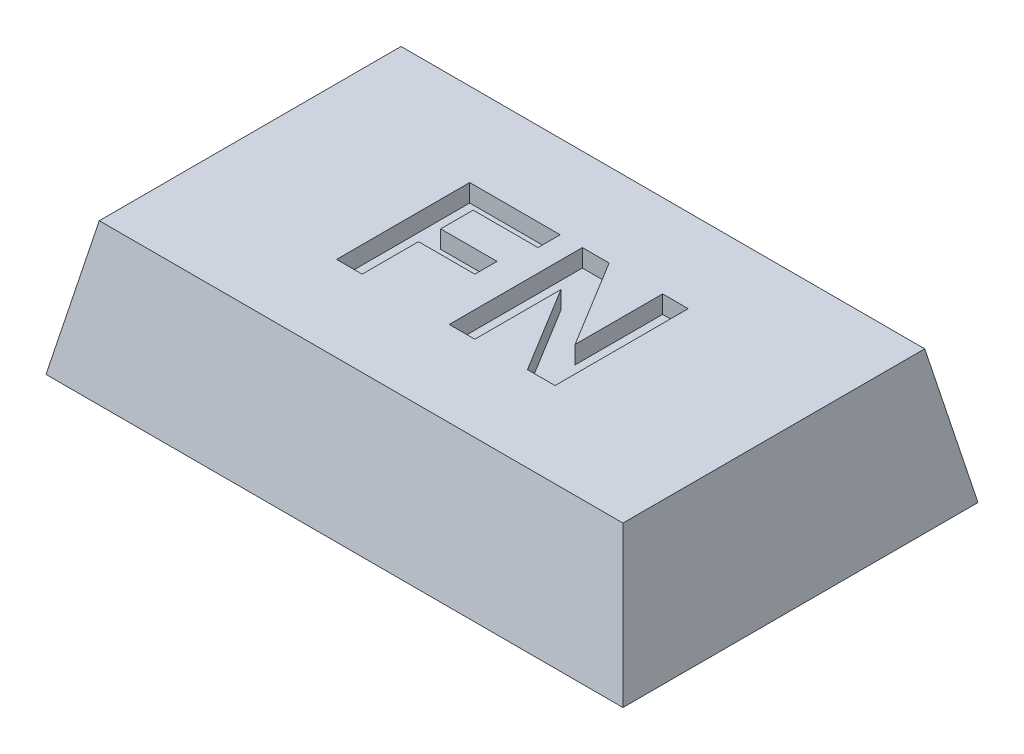
SolidWorks part; units mm, degrees
ref_plane "Front Plane" through (0, 0, 0) normal (0, 0, 1) x (1, 0, 0)
ref_plane "Top Plane" through (0, 0, 0) normal (0, 1, 0) x (1, 0, 0)
ref_plane "Right Plane" through (0, 0, 0) normal (1, 0, 0) x (0, 0, -1)
sketch "Sketch1" plane through (0, 0, 0) normal (0, 1, 0) x (1, 0, 0)
  line L1 (0, 0) -> (13, 0)
  line L2 (0, 0) -> (0, 8)
  line L3 (0, 8) -> (13, 8)
  line L4 (13, 0) -> (13, 8)
  dimension "D1" = 8
  dimension "D2" = 13
extrude "Boss-Extrude1" add sketch "Sketch1" along normal blind 3
sketch "Sketch2" plane through (0, 0, 0) normal (0, 0, 1) x (1, 0, 0)
  line L0 (0, 0) -> (0.6, 3)
  line L1 (0, 3) -> (13, 3) construction
  line L2 (0.6, 3) -> (0, 3)
  line L3 (0, 3) -> (0, 0)
  line L4 (13, 0) -> (12.4, 3)
  line L5 (12.4, 3) -> (13, 3)
  line L6 (13, 3) -> (13, 0)
  dimension "D1" = 0.6
  dimension "D2" = 0.6
extrude "Cut-Extrude1" cut sketch "Sketch2" against normal through all both and the other way through all
sketch "Sketch3" plane through (0, 0, 0) normal (1, 0, 0) x (0, 0, -1)
  line L0 (0, 0) -> (0.6, 3)
  line L1 (8, 3) -> (0, 3) construction
  line L2 (0.6, 3) -> (0, 3)
  line L3 (0, 3) -> (0, 0)
  line L4 (8, 3) -> (7.4, 3)
  line L5 (7.4, 3) -> (8, 0)
  line L6 (8, 3) -> (8, 0)
  dimension "D1" = 0.6
  dimension "D2" = 0.6
extrude "Cut-Extrude2" cut sketch "Sketch3" along normal through all both and the other way through all
sketch "Sketch4" plane through (0, 0, 0) normal (0, -1, 0) x (1, 0, 0)
  line L1 (6.5, 0) -> (6.5, -8) construction
  line L2 (13, -8) -> (0, -8) construction
  line L3 (0, 0) -> (13, 0) construction
  circle A0 centre (6.5, -3.75) radius 1.8
  dimension "D1" = 3.6
  dimension "D2" = 0
  dimension "D3" = 3.75
extrude "Cut-Extrude3" cut sketch "Sketch4" against normal blind 0.8
sketch "Sketch5" plane through (0, 0, 0) normal (0, -1, 0) x (1, 0, 0)
  line L5 (0, 0) -> (13, 0) construction
  line L6 (2.5, -8) -> (10.5, -8)
  line L7 (2.5, -8) -> (2.5, -7)
  line L8 (2.5, -7) -> (10.5, -7)
  line L9 (10.5, -8) -> (10.5, -7)
  point P2 (6.5, 0)
  dimension "D1" = 1
  dimension "D2" = 4
  dimension "D3" = 4
extrude "Boss-Extrude2" add sketch "Sketch5" along normal blind 2
fillet "Fillet1" radius 4 2 edges at (10.5, -2, -7.5) (2.5, -2, -7.5)
sketch "Sketch6" plane through (0, 3, 0) normal (0, 1, 0) x (1, 0, 0)
  text T0 "FN" font "Arial" height 3
extrude "Cut-Extrude4" cut sketch "Sketch6" against normal blind 0.4
